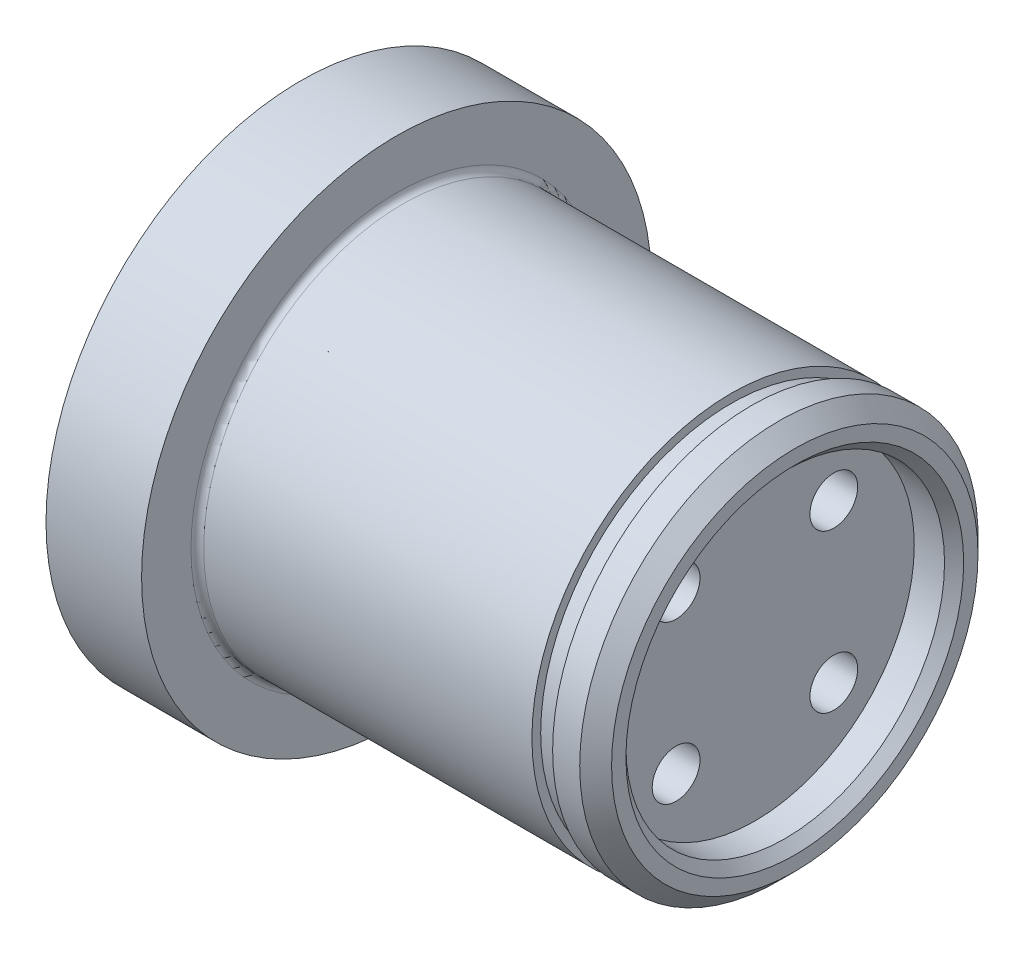
SolidWorks part; units mm, degrees
material "1060 Сплав"
ref_plane "Спереди" through (0, 0, 0) normal (0, 0, 1) x (1, 0, 0)
ref_plane "Сверху" through (0, 0, 0) normal (0, 1, 0) x (1, 0, 0)
ref_plane "Справа" through (0, 0, 0) normal (1, 0, 0) x (0, 0, -1)
sketch "Эскиз1" plane through (0, 0, 0) normal (0, 0, 1) x (1, 0, 0)
  line L0 (0, 0) -> (22138.4448, 0) construction
  line L1 (0, 0) -> (0, 12.5)
  line L2 (0, 12.5) -> (-25, 12.5)
  line L3 (-25, 12.5) -> (-25, 16)
  line L4 (-25, 16) -> (-31, 16)
  line L5 (-31, 16) -> (-31, 0)
  line L8 (0, 0) -> (-31, 0)
  dimension "D1" = 31
  dimension "D2" = 6
  dimension "D3" = 25
  dimension "D6" = 32
revolve "Повернуть1" add sketch "Эскиз1" angle 360 about L0
sketch "Эскиз2" plane through (0, 0, 0) normal (0, 0, 1) x (1, 0, 0)
  line L0 (-4, 12.5) -> (-4, 11.95)
  line L1 (0, 12.5) -> (-25, 12.5) construction
  line L2 (-4, 11.95) -> (-2.7, 11.95)
  line L3 (-2.7, 11.95) -> (-2.7, 12.5)
  line L4 (-2.7, 12.5) -> (-4, 12.5)
  line L5 (0, -12.5) -> (0, 12.5) construction
  line L6 (0, 0) -> (-50000, 0) construction
  point P10 (-2.7, 12.225)
  point P13 (0, 0)
  dimension "D1" = 4
  dimension "D2" = 1.3
  dimension "D3" = 23.9
revolve "Вырез-Повернуть1" cut sketch "Эскиз2" angle 360 about L6
chamfer "Фаска1" distance 1 angle 45 1 edges at (0, 0, 12.5)
fillet "Скругление1" radius 0.4 1 edges at (-25, 0, 12.5)
hole_wizard "Отверстие1" positions "Эскиз3" profile "Эскиз4" legacy end condition through all
sketch "Эскиз3" plane through (0, 0, 0) normal (1, 0, 0) x (0, 0, -1)
  line L0 (0, 0) -> (0, 7) construction
  line L2 (0, 0) -> (4.9497, 4.9497) construction
  circle A0 centre (0, 0) radius 7 construction
  point P0 (4.9497, 4.9497)
  dimension "D1" = 14
  dimension "D2" = 45
sketch "Эскиз4" plane through (0, 4.9497, -4.9497) normal (0, 1, 0) x (0, 0, -1)
  line L0 (0, 0) -> (0, 31)
  line L1 (0, 31) -> (1.5, 31)
  line L2 (1.5, 31) -> (1.5, 0)
  line L3 (1.5, 0) -> (0, 0)
  line L4 (0, 110) -> (0, -10) construction
  dimension "Диаметр" = 3
  dimension "Глубина" = 31
pattern_circular "Круговой массив1" count 4 over 360 about axis through (0, 0, 0) along (-1, 0, 0) of "Отверстие1"
sketch "Эскиз5" plane through (0, 0, 0) normal (0, 0, 1) x (1, 0, 0)
  line L0 (0, 0) -> (0, 10)
  line L1 (0, -11.5) -> (0, 11.5) construction
  line L7 (0, 10) -> (-2.5, 10)
  line L8 (-2.5, 10) -> (-2.5, 0)
  line L9 (-2.5, 0) -> (0, 0)
  line L10 (0, 0) -> (-50000, 0) construction
  dimension "D1" = 2.5
  dimension "D2" = 20
revolve "Вырез-Повернуть2" cut sketch "Эскиз5" angle 360 about L10
chamfer "Фаска2" distance 0.6 angle 45 1 edges at (0, 0, -10)
